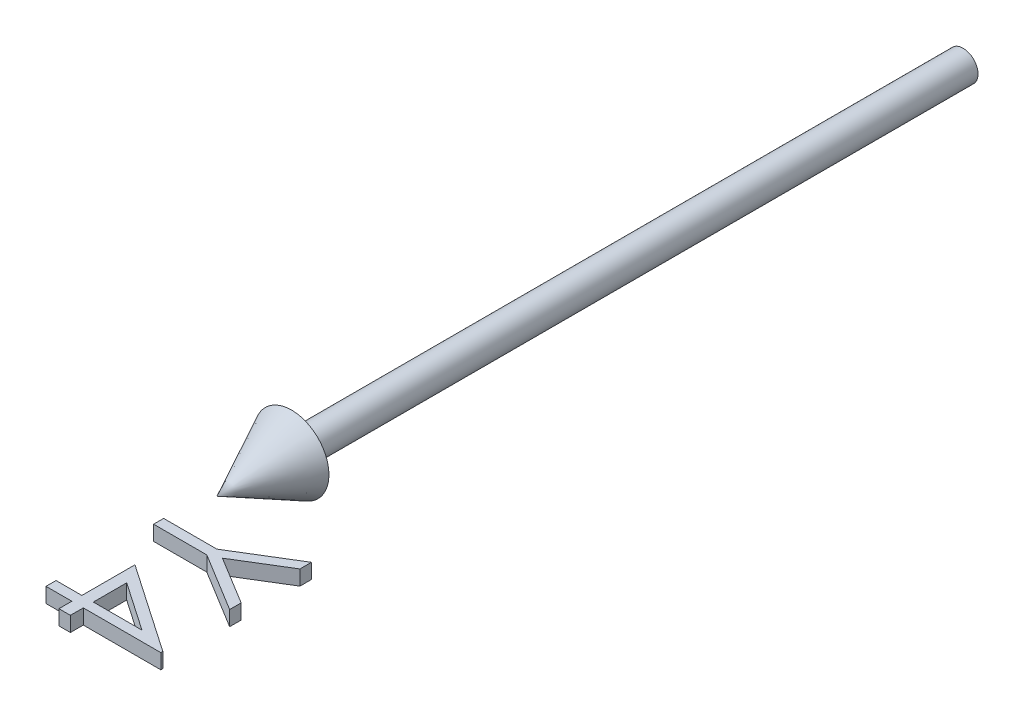
SolidWorks part; units mm, degrees
ref_plane "Front Plane" through (0, 0, 0) normal (0, 0, 1) x (1, 0, 0)
ref_plane "Top Plane" through (0, 0, 0) normal (0, 1, 0) x (1, 0, 0)
ref_plane "Right Plane" through (0, 0, 0) normal (1, 0, 0) x (0, 0, -1)
sketch "Sketch2" plane through (0, 0, 0) normal (0, 1, 0) x (1, 0, 0)
  line L0 (0, 41.95) -> (0, -114.4521) construction
  line L1 (-36.8894, 0) -> (41.4965, 0) construction
  line L2 (0, -100) -> (5, -90)
  line L3 (5, -90) -> (2, -90)
  line L4 (2, -90) -> (2, 0)
  line L5 (2, 0) -> (0, 0)
  line L6 (0, 0) -> (0, -100)
  dimension "D1" = 100
  dimension "D2" = 2
  dimension "D3" = 10
  dimension "D4" = 5
revolve "Revolve1" add sketch "Sketch2" angle 360 about L0
sketch "Sketch3" plane through (0, 0, 0) normal (0, 1, 0) x (1, 0, 0)
  line L0 (0, -101.5706) -> (0, -127.8138) construction
  text T0 "Y4\r\n\r\n" font "Century Gothic" height 15
extrude "Boss-Extrude1" add sketch "Sketch3" against normal blind 1 and the other way blind 1 separate body
equation "\"frame_arrow_length\"=100"
equation "\"D1@Sketch2\"=\"frame_arrow_length\""
equation "\"frame_arrow_odA\"=4"
equation "\"D2@Sketch2\"=\"frame_arrow_odA\"/2"
equation "\"frame_arrow_head_od\"=5"
equation "\"D4@Sketch2\"=\"frame_arrow_head_od\""
equation "\"frame_arrow_head_length\"=10"
equation "\"D3@Sketch2\"=\"frame_arrow_head_length\""
equation "\"tvarobot_theta1\"=30"
equation "\"link0_ringA_odA\"= 40"
equation "\"link0_ringA_odB\"= 25"
equation "\"link0_ringA_id\"= 20"
equation "\"link0_ringA_thickness\"= (\"link0_ringA_odB\" - \"link0_ringA_id\")/2"
equation "\"link0_ringA_height\"= 3"
equation "\"link0_ringA_heightA\"= 1.5"
equation "\"link0_ringA_heightB\"=\"link0_ringA_height\"-\"link0_ringA_heightA\""
equation "\"link0_ringB_odA\"= 40"
equation "\"link0_ringB_odB\"= 29"
equation "\"link0_ringB_id\"= \"link0_shaftA_bearing_id\"+1"
equation "\"link0_ringB_thickness\"= (\"link0_ringB_odB\" - \"link0_ringB_id\")/2"
equation "\"link0_ringB_height\"= 3"
equation "\"link0_ringB_heightA\"= 1.5"
equation "\"link0_ringB_heightB\"=\"link0_ringB_height\"-\"link0_ringB_heightA\""
equation "\"link0_shaftA_bearing_od\"=27"
equation "\"link0_shaftA_bearing_id\"=20"
equation "\"link0_shaftA_thrust_bearing_od\"=35"
equation "\"link0_shaftA_thrust_bearing_id\"=20.04"
equation "\"link0_shaftA_retaining_ring_id\"=18.5"
equation "\"link0_shaftA_retaining_ring_groove_width\"=1.5"
equation "\"link0_shaftA_spline_length\"=8.0"
equation "\"link0_shaftA_spline_depth\"=1.0"
equation "\"link0_shaftA_spline_width\"=4.0"
equation "\"link0_shaftA_odA\"=\"link0_shaftA_bearing_id\""
equation "\"link0_shaftA_odB\"=35"
equation "\"link0_shaftA_odC\"=\"link0_shaftA_bearing_id\""
equation "\"link0_shaftA_odD\"=\"link0_shaftA_odC\"-2*\"link0_shaftA_spline_depth\""
equation "\"link0_shaftA_odE\"=\"link0_shaftA_bearing_id\""
equation "\"link0_shaftA_odF\"=\"link0_shaftA_odE\"-2*\"link0_shaftA_spline_depth\""
equation "\"link0_shaftA_idA\"=10"
equation "\"link0_shaftA_idB\"=6"
equation "\"link0_shaftA_length\"=39.5"
equation "\"link0_shaftA_lengthA\"=8.0"
equation "\"link0_shaftA_lengthB\"=12.0"
equation "\"link0_shaftA_lengthC\"=35.0"
equation "\"link0_shaftA_lengthD\"=39.0"
equation "\"link0_shaftA_lengthE\"=\"link0_shaftA_length\"-\"link0_shaftA_lengthD\""
equation "\"link0_shaftA_offsetX\"=11"
equation "\"link0_shaftA_offsetY\"=0"
equation "\"link0_shaftA_bolt_pattern_dia\"=14"
equation "\"link0_motor_center_dist\"=26"
equation "\"link0_46t_pulley_spline_length\"=8"
equation "\"link0_46t_pulley_spline_depth\"=\"link0_shaftA_spline_depth\"*1.025"
equation "\"link0_46t_pulley_spline_width\"=\"link0_shaftA_spline_width\"*1.05"
equation "\"link0_46t_pulley_idA\"=\"link0_shaftA_bearing_id\"*1.025"
equation "\"link0_46t_pulley_idB\"=\"link0_46t_pulley_idA\"-2*\"link0_46t_pulley_spline_depth\""
equation "\"link0_shaftB_spline_length\"=10"
equation "\"link0_shaftB_spline_depth\"=1.0"
equation "\"link0_shaftB_spline_width\"=1.25"
equation "\"link0_shaftB_length\"=7"
equation "\"link0_shaftB_lengthA\"=1.5"
equation "\"link0_shaftB_lengthB\"=2.75"
equation "\"link0_shaftB_odA\"=32"
equation "\"link0_shaftB_odB\"=22"
equation "\"link0_shaftB_odC\"=20"
equation "\"link0_shaftB_idA\"=10"
equation "\"link0_shaftB_bolt_diameter\"=19"
equation "\"link0_shaftB_bearing_od\"=27"
equation "\"link0_shaftB_bearing_id\"=20"
equation "\"link0_motor_length\"=46.5"
equation "\"link0_motor_width\"=28.5"
equation "\"link0_motor_height\"=34"
equation "\"link0_motor_offset\"=8"
equation "\"link0_shellA_thickness\"=2.5"
equation "\"link0_shellB_thickness\"=\"link0_shellA_thickness\""
equation "\"link0_plateA_shellA_height\"=48"
equation "\"link0_shellA_width\" =\"link0_plateA_width\""
equation "\"link0_shellA_height\" = \"link0_plateA_shellA_height\"-\"link0_plateA_height\""
equation "\"link0_shellA_length\" = \"link0_plateA_lengthB\" "
equation "\"link0_shellB_length\"=\"link0_shellA_length\""
equation "\"link0_shellA_radius\" = 0.375*25.4"
equation "\"link0_shellA_radiusA\"= \"link0_plateA_radiusA\""
equation "\"link0_shellA_radiusB\"= \"link0_plateA_radiusB\""
equation "\"link0_shellA_radiusC\"= 3"
equation "\"link0_postA_height\"=7"
equation "\"link0_postA_width\"=16"
equation "\"link0_postA_length\"=20"
equation "\"link0_postA_posX\"=22"
equation "\"link0_postA_posY\"=17.5"
equation "\"link0_postA_pocket_width\"=6.0"
equation "\"link0_postA_pocket_length\"=2.5"
equation "\"link0_postA_pocket_depth\"=9"
equation "\"link0_postA_pocket_posZ\"=10"
equation "\"link0_postB_height\"=7"
equation "\"link0_postB_width\"=16"
equation "\"link0_postB_length\"=20"
equation "\"link0_postB_posX\"=22"
equation "\"link0_postB_posY\"=17.5"
equation "\"link0_postB_id\"=3.0"
equation "\"link0_postB_pocket_width\"=6.0"
equation "\"link0_postB_pocket_length\"=2.5"
equation "\"link0_postB_pocket_depth\"=9"
equation "\"link0_postB_pocket_posZ\"=10"
equation "\"link0_postC_height\"=7"
equation "\"link0_postC_width\"=16"
equation "\"link0_postC_length\"=20"
equation "\"link0_postC_posX\"=22"
equation "\"link0_postC_posY\"=17.5"
equation "\"link0_postC_id\"=3.0"
equation "\"link0_postC_pocket_width\"=6.0"
equation "\"link0_postC_pocket_length\"=2.5"
equation "\"link0_postC_pocket_depth\"=9"
equation "\"link0_postC_pocket_posZ\"=10"
equation "\"link0_postD_height\"=7"
equation "\"link0_postD_width\"=16"
equation "\"link0_postD_length\"=20"
equation "\"link0_postD_posX\"=22"
equation "\"link0_postD_posY\"=17.5"
equation "\"link0_postD_id\"=3.0"
equation "\"link0_postD_pocket_width\"=6.0"
equation "\"link0_postD_pocket_length\"=3.0"
equation "\"link0_postD_pocket_depth\"=9"
equation "\"link0_postD_pocket_posZ\"=10"
equation "\"link0_postE_height\"=5"
equation "\"link0_postE_width\"=16"
equation "\"link0_postE_length\"=\"link0_plateE_lengthA\"-\"link0_lip_height\""
equation "\"link0_postE_posZ\"=22"
equation "\"link0_postE_posX\"=17.5"
equation "\"link0_postE_posY\"=22"
equation "\"link0_postE_id\"=3.0"
equation "\"link0_postE_cbore_id\"=6.5"
equation "\"link0_postE_hole_id\"=3"
equation "\"link0_postF_posZ\"=22"
equation "\"link0_postF_posX\"=17.5"
equation "\"link0_postF_posY\"=\"link0_plateB_lengthA\"+4"
equation "\"link0_postF_id\"=3.0"
equation "\"link0_postF_cbore_id\"=6.5"
equation "\"link0_postF_hole_id\"=3"
equation "\"link0_postG_posZ\"=22"
equation "\"link0_postG_posX\"=17.5"
equation "\"link0_postG_posY\"=\"link0_plateB_lengthA\"+12"
equation "\"link0_postG_id\"=3.0"
equation "\"link0_postG_cbore_id\"=6.5"
equation "\"link0_postG_hole_id\"=3"
equation "\"link0_postHIJ_posY\"=6"
equation "\"link0_postH_posX\"=28"
equation "\"link0_postH_posY\"=20"
equation "\"link0_postH_posZ\"=20"
equation "\"link0_postH_length\"=10"
equation "\"link0_postI_posX\"=28"
equation "\"link0_postI_posY\"=20"
equation "\"link0_postI_posZ\"=135"
equation "\"link0_postI_length\"=10"
equation "\"link0_postJ_posX\"=28"
equation "\"link0_postJ_posY\"=20"
equation "\"link0_postJ_posZ\"=175"
equation "\"link0_postJ_length\"=10"
equation "\"link0_postK_posX\"=28"
equation "\"link0_postK_posY\"=20"
equation "\"link0_postK_posZ\"=175"
equation "\"link0_postK_length\"=10"
equation "\"link0_postL_posX\"=28"
equation "\"link0_postL_posY\"=20"
equation "\"link0_postL_posZ\"=135"
equation "\"link0_postL_length\"=10"
equation "\"link0_postM_posX\"=28"
equation "\"link0_postM_posY\"=20"
equation "\"link0_postM_posZ\"=35"
equation "\"link0_postM_length\"=10"
equation "\"link0_plateA_lengthA\"=30"
equation "\"link0_plateA_lengthB\"=150"
equation "\"link0_plateA_lengthC\"=30"
equation "\"link0_plateA_length\"=\"link0_plateA_lengthA\"+\"link0_plateA_lengthB\"+\"link0_plateA_lengthC\""
equation "\"link0_plateA_width\"=  68"
equation "\"link0_plateA_height\"= \"link0_plateA_radiusA\""
equation "\"link0_plateA_thickness\"=\"link0_shellA_thickness\""
equation "\"link0_plateA_radius\"= 9.5"
equation "\"link0_plateA_radiusA\"= 18"
equation "\"link0_plateA_radiusB\"= 18"
equation "\"link0_plateA_radiusC\"= 3"
equation "\"link0_plateB_length\"= 40"
equation "\"link0_plateB_width\"= \"link0_plateA_width\"*1.005"
equation "\"link0_plateB_height\"= \"link0_plateA_shellA_height\"*1.005"
equation "\"link0_plateB_lengthA\"=\"link0_lip_height\"+\"link0_plateD_thickness\"+\"link0_motor_mount_thickness\""
equation "\"link0_plateB_lengthB\"=\"link0_plateB_height\"-\"link0_plateB_lengthA\""
equation "\"link0_plateB_radiusA\"= \"link0_plateA_radiusA\""
equation "\"link0_plateB_radiusB\"= \"link0_plateA_radiusB\""
equation "\"link0_plateB_radiusC\"= 3"
equation "\"link0_plateB_idA\"=\"link0_shaftA_odC\"+1"
equation "\"link0_plateB_idB\"=\"link0_shaftA_bearing_od\"-2"
equation "\"link0_plateB_idC\"=\"link0_shaftA_bearing_od\"*1.005"
equation "\"link0_plateB_idD\"=\"link0_shaftA_thrust_bearing_od\"+1 "
equation "\"link0_plateB_depthA\"=1.0"
equation "\"link0_plateB_depthB\"=2.0"
equation "\"link0_plateB_depthC\"=8"
equation "\"link0_plateB_depthD\"=\"link0_plateB_length\"-\"link0_lip_height\"-\"link0_plateD_thickness\" "
equation "\"link0_plateC_length\"=\"link0_plateB_length\""
equation "\"link0_plateC_width\"= \"link0_plateB_width\""
equation "\"link0_plateC_height\"= .1*25.4"
equation "\"link0_plateA_hole_od\" = 0.1*25.4"
equation "\"link0_plateA_hole_delx\" = 0.5*25.4"
equation "\"link0_plateA_hole_delz\" = 0.75*25.4"
equation "\"link0_plateA_hole_offx\" = 0.0*25.4"
equation "\"link0_plateA_hole_offz\" = \"link0_plateA_length\"/2"
equation "\"link0_plateB_hole_od\" = 0.1*25.4"
equation "\"link0_plateB_hole_delx\"= 0.75*25.4"
equation "\"link0_plateB_hole_delz\"= 0.75*25.4"
equation "\"link0_plateB_hole_offx\"= 0.0*25.4"
equation "\"link0_plateB_hole_offz\"= 0.0*25.4"
equation "\"link0_plateC_hole_od\"= 0.1*25.4"
equation "\"link0_plateC_hole_delx\"= 0.75*25.4"
equation "\"link0_plateC_hole_delz\"= 0.75*25.4"
equation "\"link0_plateC_hole_offx\"= 0.0*25.4"
equation "\"link0_plateC_hole_offz\"= 0.0*25.4"
equation "\"link0_plateD_height\"=\"link0_plateB_height\"-2*\"link0_shellA_thickness\""
equation "\"link0_plateD_width\"=\"link0_plateB_width\"-2*\"link0_shellA_thickness\""
equation "\"link0_plateD_thickness\"=10"
equation "\"link0_plateD_radiusA\"=\"link0_plateB_radiusA\"-\"link0_shellA_thickness\""
equation "\"link0_plateD_odA\"= .375*25.4"
equation "\"link0_plateD_odB\"= .375*25.4"
equation "\"link0_plateD_bearing_id\"=20"
equation "\"link0_plateD_bearing_od\"=27"
equation "\"link0_plateE_radiusA\"=\"link0_plateA_radiusA\""
equation "\"link0_plateE_radiusB\"=\"link0_plateA_radiusB\""
equation "\"link0_plateE_radiusC\"=8.0"
equation "\"link0_plateE_length\"=30"
equation "\"link0_plateE_lengthA\"=16"
equation "\"link0_plateE_height\"=\"link0_plateB_height\""
equation "\"link0_plateE_width\"=\"link0_plateB_width\""
equation "\"link0_plateE_odA\"=\"gantry_coupler_id\"*0.99"
equation "\"link0_plateE_idA\"=\"link0_plateE_odA\"-20.0"
equation "\"link0_plateE_spline_depth\"=\"link0_poleA_spline_depth\"*1.05"
equation "\"link0_plateE_spline_width\"=\"link0_poleA_spline_width\"*1.075"
equation "\"link0_plateE_spline_length\"=\"link0_poleA_spline_length\""
equation "\"link0_plateE_coupler_length\"=46"
equation "\"link0_lip_height\"=5.0"
equation "\"link0_lip_thickness\"=2.0"
equation "\"link0_motor_mount_thickness\"=8.0"
equation "\"link0_motor_mount_idA\"=22"
equation "\"link0_motor_mount_idB\"=\"link0_shaftB_bearing_od\"*1.005"
equation "\"link0_motor_mount_idC\"=\"link0_shaftB_bearing_od\"-2"
equation "\"link0_motor_mount_depthA\"=5.5"
equation "\"link0_motor_mount_height\"=\"link0_plateD_height\""
equation "\"link0_motor_mount_width\"=\"link0_plateD_width\""
equation "\"link0_motor_mountL_height\"=36"
equation "\"link0_motor_mountL_heightA\"=12"
equation "\"link0_motor_mountL_length\"=50"
equation "\"link0_motor_mountL_lengthA\"=36"
equation "\"gantry_coupler_od\"=25.4*2.0"
equation "\"gantry_coupler_id\"=1.645*25.4"
equation "\"gantry_coupler_offsetX\"=\"link0_plateE_width\"/2"
equation "\"link0_poleA_odA\"=20"
equation "\"link0_poleA_odB\"=36"
equation "\"link0_poleA_idA\"=\"link0_poleA_odA\"-2*\"link0_poleA_thickness\""
equation "\"link0_poleA_idB\"=(\"link0_plateE_idA\"/2+1.5*\"link0_lip_thickness\")*1.04"
equation "\"link0_poleA_thickness\"=3.5"
equation "\"link0_poleA_length\"=100"
equation "\"link0_poleA_lengthA\"=18.5"
equation "\"link0_poleA_lengthB\"=80"
equation "\"link0_poleA_gasket_thickness\"=1.5"
equation "\"link0_poleA_spline_depth\"=1.0"
equation "\"link0_poleA_spline_width\"=4.0"
equation "\"link0_poleA_spline_length\"=10.0"
equation "\"link1_plateB_length\"=30"
equation "\"link1_lip_height\"=\"link0_lip_height\""
equation "\"link0_tension_plateA_width\"=12"
equation "\"link0_tension_plateA_lengthA\"=10.5"
equation "\"link0_tension_plateB_width\"=\"link0_tension_plateA_width\""
equation "\"link0_tension_plateB_lengthA\"=\"link0_tension_plateA_lengthA\""
equation "\"link0_tension_wheelA_posZ\"=7"
equation "\"link0_tension_wheelA_posX\"=\"link0_plateD_height\"/2-\"link0_tension_plateA_lengthA\""
equation "\"link0_m2_clear_hole_id\"=2.35"
equation "\"link0_m2_insert_hole_id\"=2.5"
equation "\"link0_m2_tap_hole_id\"=1.75"
equation "\"link0_m2_nut_socket_width\"=4.25"
equation "\"link0_m2_nut_socket_depth\"=2.5"
equation "\"link0_m2_cbore_id\"=3.75"
equation "\"link0_m2_cbore_depth\"=7"
equation "\"link0_m2_5_clear_hole_id\"=2.75"
equation "\"link0_m2_5_insert_hole_id\"=2.75"
equation "\"link0_m2_5_tap_hole_id\"=2.25"
equation "\"link0_m2_5_nut_socket_width\"=5.25"
equation "\"link0_m2_5_nut_socket_depth\"=2.5"
equation "\"link0_m2_5_cbore_id\"=4.75"
equation "\"link0_m2_5_cbore_depth\"=2.5"
equation "\"link0_m2_5_insert_access_length\"=6.0"
equation "\"link0_m2_5_insert_access_width\"=3.0"
equation "\"link0_m3_clear_hole_id\"=3.25"
equation "\"link0_m3_insert_hole_id\"=3"
equation "\"link0_m3_tap_hole_id\"=2.75"
equation "\"link0_m3_nut_socket_width\"=5.75"
equation "\"link0_m3_nut_socket_depth\"=4.0"
equation "\"link0_m3_cbore_id\"=5.75"
equation "\"link0_m3_cbore_depth\"=3.5"
equation "\"link0_m3_insert_access_length\"=4.5"
equation "\"link0_m3_insert_access_width\"=3.5"
equation "\"link0_rpi_mount_height\"=6"
equation "\"link0_rpi_mount_width\"=49"
equation "\"link0_rpi_mount_length\"=58"
equation "\"link0_rpi_mount_post_od\"=6"
equation "\"link0_rpi_mount_posZ\"=72"
equation "\"link0_rpi_mount_posX\"=11.5"
equation "\"link0_mcu_mount_height\"=5"
equation "\"link0_mcu_mount_width\"=49"
equation "\"link0_mcu_mount_length\"=58"
equation "\"link0_mcu_mount_post_od\"=6"
equation "\"link0_mcu_mount_posZ\"=164"
equation "\"link0_mcu_mount_posX\"=4"
equation "\"link0_pwr_mount_height\"=4"
equation "\"link0_pwr_mount_width\"=15.75"
equation "\"link0_pwr_mount_length\"=75.75"
equation "\"link0_pwr_mount_post_od\"=6"
equation "\"link0_pwr_mount_posZ\"=75"
equation "\"link0_pwr_mount_posX\"=16"
equation "\"link0_pwr_board_height\"=6"
equation "\"link0_pwr_board_width\"=21"
equation "\"link0_pwr_board_length\"=80"
